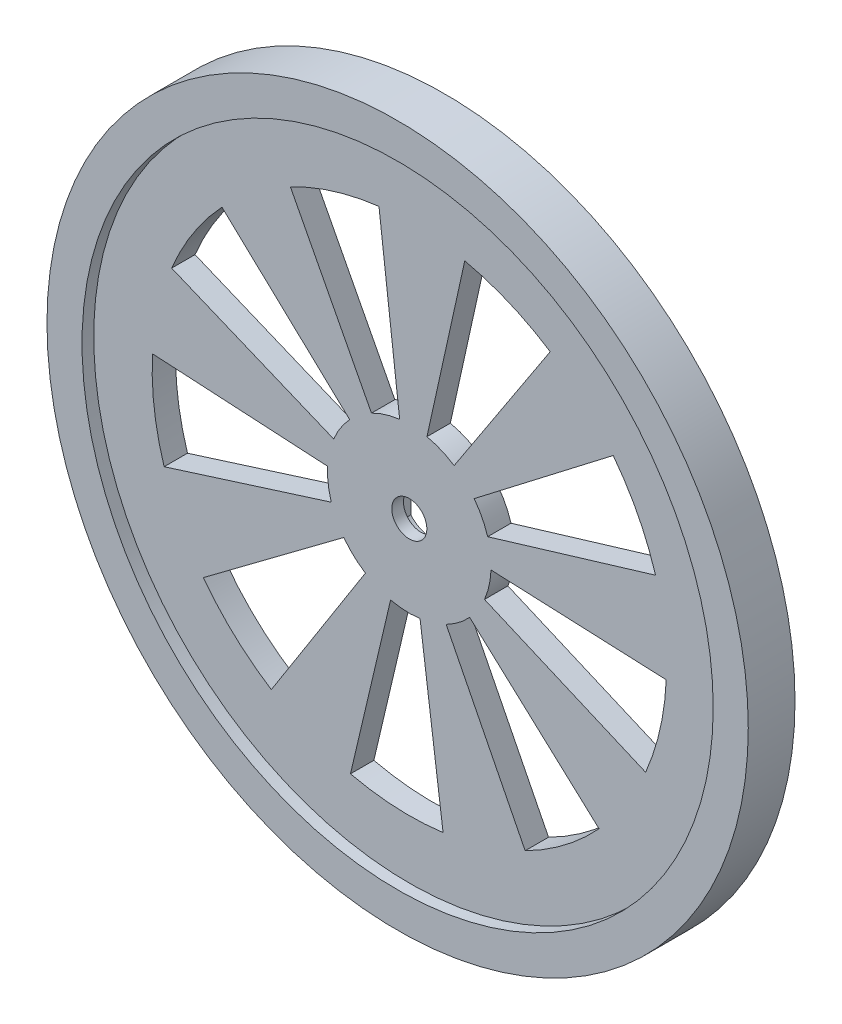
SolidWorks part; units mm, degrees
note: The reader was unsure of these and kept them because the rebuilt part matched: shared geometry of "Esquisse1<3>", "Esquisse2<3>", "Esquisse2<4>".
ref_plane "Plan de face" through (0, 0, 0) normal (0, 0, 1) x (1, 0, 0)
ref_plane "Plan de dessus" through (0, 0, 0) normal (0, 1, 0) x (1, 0, 0)
ref_plane "Plan de droite" through (0, 0, 0) normal (1, 0, 0) x (0, 0, -1)
sketch "Esquisse1" plane through (0, 0, 0) normal (0, 0, 1) x (1, 0, 0)
  line L6 (9.8994, -12.8536) -> (9.8994, -9.5464)
  line L7 (6.1494, -9.5464) -> (6.1494, -12.8536)
  circle A0 centre (8.0244, -11.2) radius 30
  arc A8 (8.0244, -12.7) -> (8.0244, -9.7) centre (8.0244, -11.2) ccw
  arc A9 (8.0244, -9.7) -> (8.0244, -12.7) centre (8.0244, -11.2) ccw
  arc A14 (9.8994, -9.5464) -> (8.0244, -8.7) centre (8.0244, -11.2) ccw
  arc A15 (8.0244, -8.7) -> (6.1494, -9.5464) centre (8.0244, -11.2) ccw
  arc A16 (6.1494, -12.8536) -> (8.0244, -13.7) centre (8.0244, -11.2) ccw
  arc A17 (8.0244, -13.7) -> (9.8994, -12.8536) centre (8.0244, -11.2) ccw
  dimension "D2" = 60
extrude "Boss.-Extru.1" add sketch "Esquisse1" along normal blind 4 from offset 2 contours A0 A17 A16 L7 A15 A14 L6 offset against normal yes
extrude "Boss.-Extru.2" add sketch "Esquisse1<3>" along normal blind 2 contours A16 A17 L6 A14 A15 L7 A9 A8
sketch "Esquisse1<3>" plane through (0, 0, 0) normal (0, 0, 1) x (1, 0, 0) same geometry as "Esquisse1"
sketch "Esquisse2" plane through (0, 0, 2) normal (0, 0, 1) x (1, 0, 0)
  line L16 (-9.5972, -24.3711) -> (2.4175, -15.3908)
  line L17 (-3.7812, -29.7641) -> (4.2681, -17.1068)
  line L18 (-13.9408, -9.9627) -> (1.0355, -10.8063)
  line L19 (-12.952, -17.8324) -> (1.3501, -13.3103)
  line L20 (-8.0066, 3.8668) -> (2.9237, -6.406)
  line L21 (-12.3077, -2.7973) -> (1.5551, -8.5264)
  line L22 (5.4287, 10.6463) -> (7.1985, -4.2489)
  line L23 (-2.1498, 8.306) -> (4.7872, -4.9935)
  line L24 (20.0785, 7.2037) -> (11.8598, -5.3443)
  line L25 (12.7688, 10.2823) -> (9.534, -4.3647)
  line L26 (29.0881, -4.8502) -> (14.7265, -9.1796)
  line L27 (25.4674, 2.2068) -> (13.5745, -6.9342)
  line L28 (28.2417, -19.8752) -> (14.4572, -13.9603)
  line L29 (30.0042, -12.1419) -> (15.018, -11.4997)
  line L30 (17.9355, -30.8411) -> (11.1779, -17.4494)
  line L31 (24.2565, -26.0499) -> (13.1892, -15.925)
  line L32 (2.9917, -32.6166) -> (6.4231, -18.0144)
  line L33 (10.9136, -33.0095) -> (8.9437, -18.1394)
  arc A2 (-9.5972, -24.3711) -> (-3.7812, -29.7641) centre (8.0244, -11.2) ccw
  arc A19 (2.4175, -15.3908) -> (4.2681, -17.1068) centre (8.0244, -11.2) ccw
  circle A20 centre (8.0244, -11.2) radius 30 construction
  circle A21 centre (8.0244, -11.2) radius 27
  arc A22 (-13.9408, -9.9627) -> (-12.952, -17.8324) centre (8.0244, -11.2) ccw
  arc A23 (1.0355, -10.8063) -> (1.3501, -13.3103) centre (8.0244, -11.2) ccw
  arc A24 (-8.0066, 3.8668) -> (-12.3077, -2.7973) centre (8.0244, -11.2) ccw
  arc A25 (2.9237, -6.406) -> (1.5551, -8.5264) centre (8.0244, -11.2) ccw
  arc A26 (5.4287, 10.6463) -> (-2.1498, 8.306) centre (8.0244, -11.2) ccw
  arc A27 (7.1985, -4.2489) -> (4.7872, -4.9935) centre (8.0244, -11.2) ccw
  arc A28 (20.0785, 7.2037) -> (12.7688, 10.2823) centre (8.0244, -11.2) ccw
  arc A29 (11.8598, -5.3443) -> (9.534, -4.3647) centre (8.0244, -11.2) ccw
  arc A30 (29.0881, -4.8502) -> (25.4674, 2.2068) centre (8.0244, -11.2) ccw
  arc A31 (14.7265, -9.1796) -> (13.5745, -6.9342) centre (8.0244, -11.2) ccw
  arc A32 (28.2417, -19.8752) -> (30.0042, -12.1419) centre (8.0244, -11.2) ccw
  arc A33 (14.4572, -13.9603) -> (15.018, -11.4997) centre (8.0244, -11.2) ccw
  arc A34 (17.9355, -30.8411) -> (24.2565, -26.0499) centre (8.0244, -11.2) ccw
  arc A35 (11.1779, -17.4494) -> (13.1892, -15.925) centre (8.0244, -11.2) ccw
  arc A36 (2.9917, -32.6166) -> (10.9136, -33.0095) centre (8.0244, -11.2) ccw
  arc A37 (6.4231, -18.0144) -> (8.9437, -18.1394) centre (8.0244, -11.2) ccw
  dimension "D1" = 8
  dimension "D2" = 23
  dimension "D3" = 3
extrude "Enlèv. mat.-Extru.1" cut sketch "Esquisse2" against normal blind 12 contours A35 L30 A34 L31 | A33 L28 A32 L29 | A37 L32 A36 L33 | A19 L16 A2 L17 | A23 L18 A22 L19 | A25 L20 A24 L21 | A27 L22 A26 L23 | A29 L24 A28 L25 | A31 L26 A30 L27
extrude "Enlèv. mat.-Extru.2" cut sketch "Esquisse2<3>" against normal blind 1
sketch "Esquisse2<3>" plane through (0, 0, 2) normal (0, 0, 1) x (1, 0, 0) same geometry as "Esquisse2"
extrude "Enlèv. mat.-Extru.3" cut sketch "Esquisse2<4>" along normal blind 1 from offset 4
sketch "Esquisse2<4>" plane through (0, 0, 2) normal (0, 0, 1) x (1, 0, 0) same geometry as "Esquisse2"
